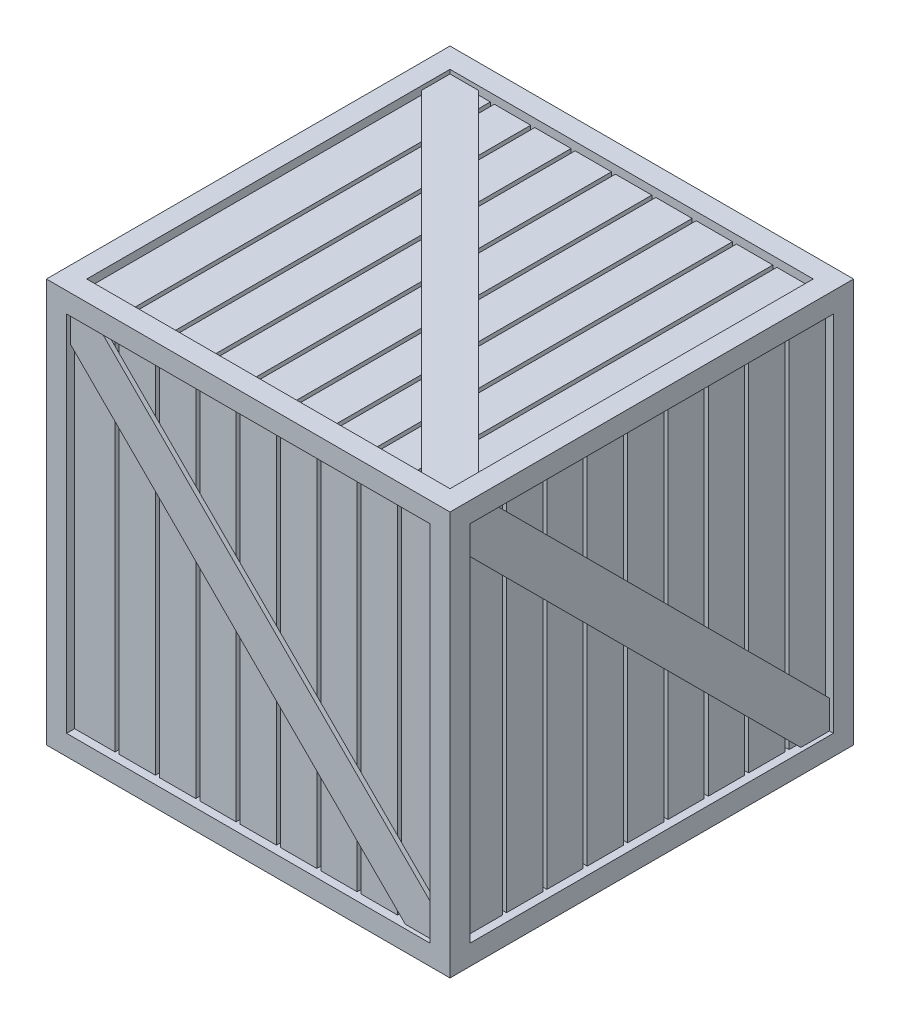
SolidWorks part; units mm, degrees
ref_plane "Front Plane" through (0, 0, 0) normal (0, 0, 1) x (1, 0, 0)
ref_plane "Top Plane" through (0, 0, 0) normal (0, 1, 0) x (1, 0, 0)
ref_plane "Right Plane" through (0, 0, 0) normal (1, 0, 0) x (0, 0, -1)
sketch "Sketch1" plane through (0, 0, 0) normal (0, 1, 0) x (1, 0, 0)
  line L1 (-50, 50) -> (50, 50)
  line L2 (-50, 50) -> (-50, -50)
  line L3 (-50, -50) -> (50, -50)
  line L4 (50, 50) -> (50, -50)
  line L5 (-50, 50) -> (50, -50) construction
  line L6 (-50, -50) -> (50, 50) construction
  point P0 (0, 0)
  dimension "D1" = 100
extrude "Boss-Extrude1" add sketch "Sketch1" along normal mid plane 100
sketch "Sketch3" plane through (0, 0, 50) normal (0, 0, 1) x (1, 0, 0)
  line L0 (50, 50) -> (50, -50) construction
  line L1 (-45, 45) -> (-37.9289, 45)
  line L2 (-45, 45) -> (-45, 37.9289)
  line L3 (37.9289, -45) -> (45, -45)
  line L4 (45, -37.9289) -> (45, -45)
  line L5 (-45, 45) -> (45, -45) construction
  line L6 (-50, 50) -> (-50, -50) construction
  line L7 (-50, -50) -> (50, -50) construction
  line L8 (-45, 37.9289) -> (37.9289, -45)
  line L9 (-37.9289, 45) -> (45, -37.9289)
  line L10 (-41.4645, 48.5355) -> (48.5355, -41.4645) construction
  line L11 (-48.5355, 41.4645) -> (41.4645, -48.5355) construction
  point P0 (0, 0)
  point P3 (-44.9803, 44.9803)
  dimension "D1" = 5
  dimension "D2" = 5
  dimension "D5" = 5
  dimension "D3" = 5
  dimension "D4" = 5
extrude "Cut-Extrude1" cut sketch "Sketch3" against normal blind 1
sketch "Sketch4" plane through (0, 0, 50) normal (0, 0, 1) x (1, 0, 0)
  line L0 (-37.9289, 45) -> (45, -37.9289)
  line L1 (-37.9289, 45) -> (45, 45)
  line L2 (-45, 37.9289) -> (-45, -45)
  line L3 (-45, -45) -> (37.9289, -45)
  line L4 (45, 45) -> (45, -37.9289)
  line L5 (-45, 45) -> (45, -45) construction
  line L6 (-45, -45) -> (45, 45) construction
  line L7 (37.9289, -45) -> (-45, 37.9289)
  point P0 (0, 0)
  point P15 (0, 0)
  line M4 (-37.9289, 45) -> (45, -37.9289)
  line M7 (37.9289, -45) -> (-45, 37.9289)
extrude "Cut-Extrude2" cut sketch "Sketch4" against normal blind 2 contours L2 L3 M7 | L4 L1 M4 | L2 L3 L7 region at (17.357, 17.357, 50) region at (-17.357, -17.357, 50)
sketch "Sketch5" plane through (0, 0, 48) normal (0, 0, 1) x (1, 0, 0)
  line L0 (-35, -45) -> (-35, 45)
  line L1 (-45, -45) -> (37.9289, -45) construction
  line L2 (-37.9289, 45) -> (-45, 45) construction
  line L3 (-35, 45) -> (-34, 45)
  line L4 (45, 45) -> (-45, 45) construction
  line L5 (-34, 45) -> (-34, -45)
  line L6 (-34, -45) -> (-35, -45)
  line L7 (-45, 45) -> (-45, -45) construction
  line L8 (-25, -45) -> (-25, 45)
  line L9 (-24, 45) -> (-24, -45)
  line L10 (-25, 45) -> (-24, 45)
  line L11 (-24, -45) -> (-25, -45)
  line L12 (-15, -45) -> (-15, 45)
  line L13 (-14, 45) -> (-14, -45)
  line L14 (-15, 45) -> (-14, 45)
  line L15 (-14, -45) -> (-15, -45)
  line L16 (-5, -45) -> (-5, 45)
  line L17 (-4, 45) -> (-4, -45)
  line L18 (-5, 45) -> (-4, 45)
  line L19 (-4, -45) -> (-5, -45)
  line L20 (5, -45) -> (5, 45)
  line L21 (6, 45) -> (6, -45)
  line L22 (5, 45) -> (6, 45)
  line L23 (6, -45) -> (5, -45)
  line L24 (15, -45) -> (15, 45)
  line L25 (16, 45) -> (16, -45)
  line L26 (15, 45) -> (16, 45)
  line L27 (16, -45) -> (15, -45)
  line L28 (25, -45) -> (25, 45)
  line L29 (26, 45) -> (26, -45)
  line L30 (25, 45) -> (26, 45)
  line L31 (26, -45) -> (25, -45)
  line L32 (35, -45) -> (35, 45)
  line L33 (36, 45) -> (36, -45)
  line L34 (35, 45) -> (36, 45)
  line L35 (36, -45) -> (35, -45)
  dimension "D1" = 1
  dimension "D2" = 10
  dimension "D4" = 10
  dimension "D3" = 8
extrude "Cut-Extrude3" cut sketch "Sketch5" against normal blind 1
ref_axis "Axis1" through (-55, 0, 0) along (1, 0, 0)
ref_axis "Axis2" through (0, 0, 55) along (0, 0, -1)
pattern_circular "CirPattern1" count 4 over 360 about axis through (-55, 0, 0) along (1, 0, 0) of "Cut-Extrude1", "Cut-Extrude3", "Cut-Extrude2"
ref_axis "Axis3" through (0, -55, 0) along (0, 1, 0)
pattern_circular "CirPattern2" count 4 over 360 about axis through (0, -55, 0) along (0, 1, 0) skipping 2 of "Cut-Extrude1", "Cut-Extrude3", "Cut-Extrude2"
